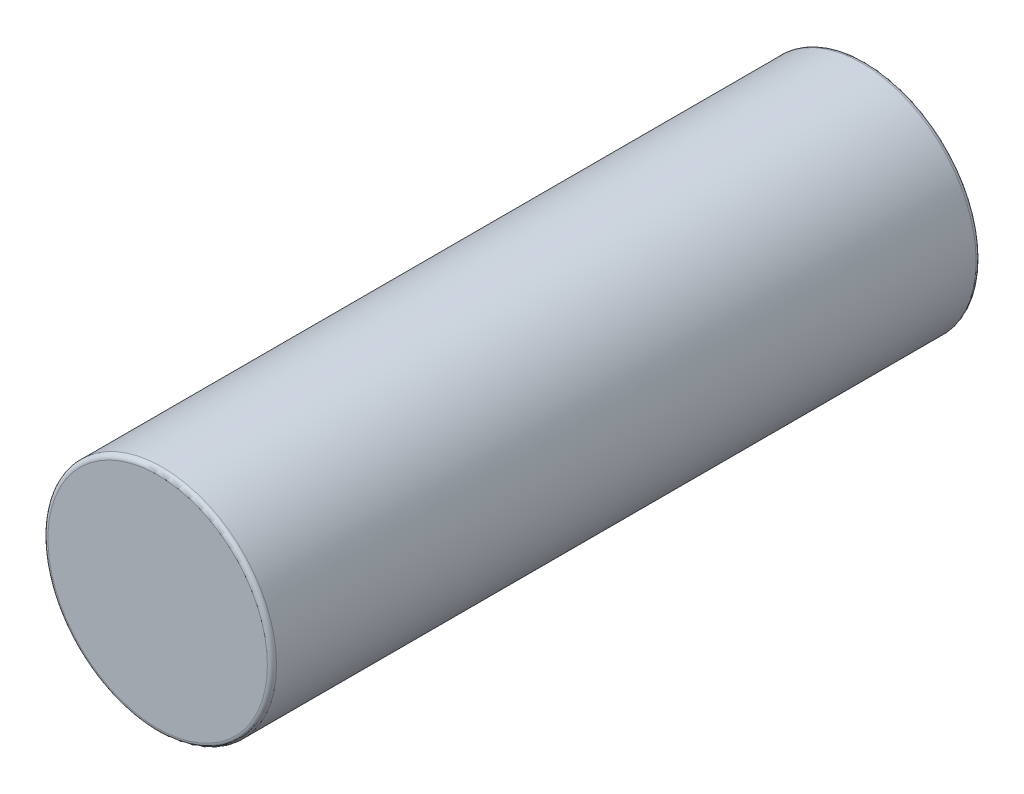
SolidWorks part; units mm, degrees
ref_plane "Front Plane" through (0, 0, 0) normal (0, 0, 1) x (1, 0, 0)
ref_plane "Top Plane" through (0, 0, 0) normal (0, 1, 0) x (1, 0, 0)
ref_plane "Right Plane" through (0, 0, 0) normal (1, 0, 0) x (0, 0, -1)
sketch "dia" plane through (0, 0, 0) normal (0, 0, 1) x (1, 0, 0)
  circle A0 centre (0, 0) radius 5
  dimension "D1" = 10
extrude "cycl" add sketch "dia" along normal blind 15.5 and the other way blind 15.5 contours A0
fillet "Fillet1" radius 0.2 2 edges at (5, 0, 15.5) (5, 0, -15.5)
sketch "center" plane through (0, 0, 0) normal (1, 0, 0) x (0, 0, -1)
  line L0 (-17.2907, 0) -> (21.5696, 0) construction
